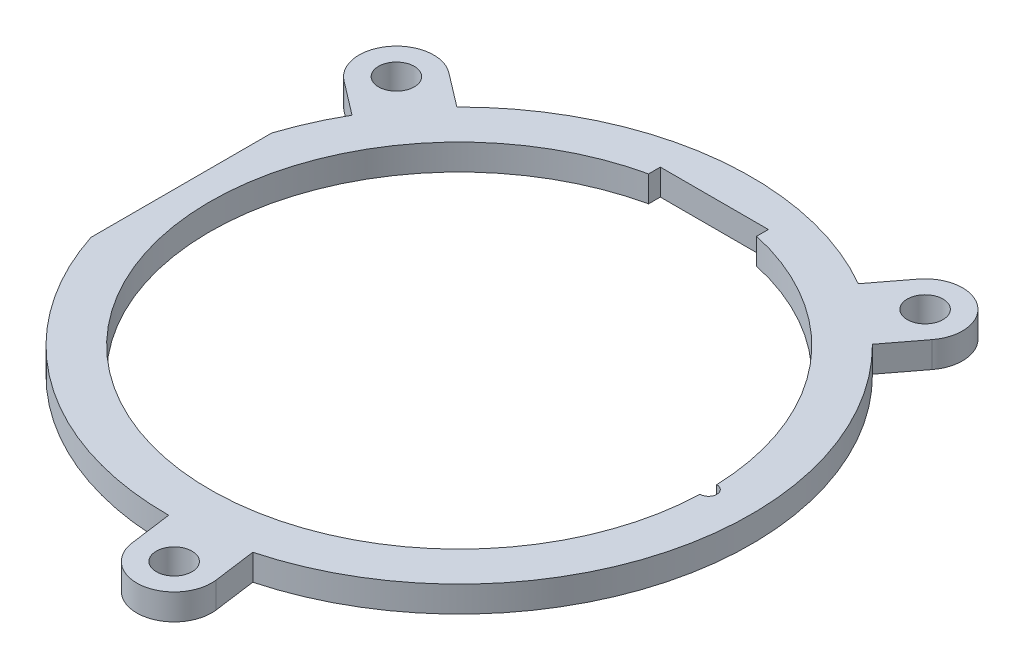
SolidWorks part; units mm, degrees
ref_plane "Front" through (0, 0, 0) normal (0, 0, 1) x (1, 0, 0)
ref_plane "Top" through (0, 0, 0) normal (0, 1, 0) x (1, 0, 0)
ref_plane "Right" through (0, 0, 0) normal (1, 0, 0) x (0, 0, -1)
sketch "Sketch1" plane through (0, 0, 0) normal (0, 1, 0) x (1, 0, 0)
  line L0 (0, -15.24) -> (0, 15.5956) construction
  line L1 (-3.302, 15.5956) -> (3.302, 15.5956)
  line L2 (-3.302, 15.5956) -> (-3.302, 14.878)
  line L3 (3.302, 15.5956) -> (3.302, 14.878)
  circle A0 centre (0, 0) radius 15.24
  circle A1 centre (0, 0) radius 21.59
  dimension "D1" = 30.48
  dimension "D3" = 30.8356
  dimension "D4" = 6.604
  dimension "D2" = 6.35
extrude "Boss-Extrude1" add sketch "Sketch1" along normal mid plane 1.5875 contours A1 A0 L2 L1 L3 region at (-20.9793, 0, 0)
sketch "Sketch2" plane through (0, 0.7937, 0) normal (0, 1, 0) x (1, 0, 0)
  line L0 (0, 18.415) -> (0, -18.415) construction
  line L1 (0, -15.24) -> (0, -21.59) construction
  circle A0 centre (0, 18.415) radius 1.4224
  circle A1 centre (0, -18.415) radius 1.4224
  arc A2 (-3.302, 14.878) -> (3.302, 14.878) centre (0, 0) ccw construction
  circle A3 centre (0, 0) radius 21.59 construction
  dimension "D1" = 2.8448
extrude "Cut-Extrude1" cut sketch "Sketch2" against normal through all
sketch "Sketch3" plane through (0, 0.7937, 0) normal (0, 1, 0) x (1, 0, 0)
  line L0 (-20.8712, 5.5245) -> (-16.9841, 5.5245)
  line L1 (-16.9841, 5.5245) -> (-16.9841, -5.5245)
  line L2 (-16.9841, -5.5245) -> (-20.8712, -5.5245)
  line L3 (-16.9841, -5.5245) -> (-20.8712, -5.5245) construction
  line L4 (-20.8712, 5.5245) -> (-16.9841, 5.5245) construction
  circle A0 centre (0, 0) radius 21.59 construction
  arc A1 (-20.8712, 5.5245) -> (-20.8712, -5.5245) centre (0, 0) ccw
extrude "Cut-Extrude2" cut sketch "Sketch3" against normal through all
sketch "Sketch4" plane through (0, 0.7937, 0) normal (0, 1, 0) x (1, 0, 0)
  line L0 (15.748, 0) -> (-15.24, 0) construction
  circle A0 centre (15.24, 0) radius 0.508
  arc A1 (-3.302, 14.878) -> (3.302, 14.878) centre (0, 0) ccw construction
  dimension "D1" = 30.988
extrude "Cut-Extrude3" cut sketch "Sketch4" against normal through all
sketch "Sketch5" plane through (0, 0.7937, 0) normal (0, 1, 0) x (1, 0, 0)
  line L0 (-12.3201, -16.1591) -> (12.3201, 16.1591) construction
  line L1 (-13.8351, -15.0041) -> (10.8052, 17.3141)
  line L2 (-10.8052, -17.3141) -> (13.8351, 15.0041)
  line L3 (16.1591, -12.3201) -> (-16.1591, 12.3201) construction
  line L4 (15.0041, -13.8351) -> (-17.3141, 10.8052)
  line L5 (17.3141, -10.8052) -> (-15.0041, 13.8351)
  line L6 (0, 0) -> (2.7145, -20.1379) construction
  line L7 (1.8879, 0.2545) -> (4.6025, -19.8834)
  line L8 (-1.8879, -0.2545) -> (0.8266, -20.3924)
  line L9 (-16.1591, 12.3201) -> (12.3201, 16.1591) construction
  circle A0 centre (0, 0) radius 17.86
  arc A1 (-13.8351, -15.0041) -> (-10.8052, -17.3141) centre (-12.3201, -16.1591) ccw
  arc A2 (13.8351, 15.0041) -> (10.8052, 17.3141) centre (12.3201, 16.1591) ccw
  circle A3 centre (12.3201, 16.1591) radius 1.0922
  circle A4 centre (-12.3201, -16.1591) radius 1.0922
  arc A5 (15.0041, -13.8351) -> (17.3141, -10.8052) centre (16.1591, -12.3201) ccw
  arc A6 (-15.0041, 13.8351) -> (-17.3141, 10.8052) centre (-16.1591, 12.3201) ccw
  circle A7 centre (-16.1591, 12.3201) radius 1.0922
  circle A8 centre (16.1591, -12.3201) radius 1.0922
  arc A9 (1.8879, 0.2545) -> (-1.8879, -0.2545) centre (0, 0) ccw
  arc A10 (0.8266, -20.3924) -> (4.6025, -19.8834) centre (2.7145, -20.1379) ccw
  circle A11 centre (2.7145, -20.1379) radius 1.0922
  arc A12 (16.1591, -12.3201) -> (2.7145, -20.1379) centre (0, 0) cw construction
  point P6 (0, 0)
  point P17 (0, 0)
  point P26 (1.3573, -10.0689)
  line M7 (-20.8712, 5.5245) -> (-16.9841, 5.5245)
  line M9 (-16.9841, -5.5245) -> (-20.8712, -5.5245)
  arc M10 (-20.8712, -5.5245) -> (-20.8712, 5.5245) centre (0, 0) ccw
  circle M11 centre (0, -18.415) radius 1.4224
  circle M12 centre (0, 18.415) radius 1.4224
  dimension "D2" = 3.81
  dimension "D1" = 3.81
extrude "Cut-Extrude4" cut sketch "Sketch5" against normal through all contours A6 L5 A0 L1 A2 M12 M10 | A6 A0 L4 M10 M7 | A1 L1 A0 M9 M10 | A5 L4 A0 L2 A1 M11 M10 | A5 A2 L2 A0 L5 M10 | A7 | A3 | A4 | A1 L2 A0 L1 A4 M10 | A11 | A5 L5 A0 L4 A8 M10 | A8 | A10 A5 L4 A0 L7 M10 region at (-16.6582, 0.7937, 10.306) region at (-13.002, 0.7937, 14.0284) region at (-5.4053, 0.7937, 18.8788) region at (-18.0946, 0.7937, -8.0783) region at (-2.5586, 0.7937, -18.0617) region at (9.8123, 0.7937, 16.8747) region at (15.6105, 0.7937, 14.0703) region at (18.0927, 0.7937, -2.4389) region at (12.3201, 0.7937, -16.1591) region at (-12.3201, 0.7937, 16.1591) region at (-16.1591, 0.7937, -12.3201) region at (16.1591, 0.7937, 12.3201) region at (2.7145, 0.7937, 20.1379)
extrude "Boss-Extrude2" add sketch "Sketch5<3>" against normal up to vertex contours A6 M10 | A2 M10 | A0 M11 | A0 M12 | A0 L8 M11 | L8 A0 M11 | A10 M10 region at (-0.2829, 0.7937, 17.4804) region at (2.9174, 0.7937, 21.6425) region at (-17.3665, 0.7937, -13.2407) region at (0, 0.7937, -17.4932) region at (0.7535, 0.7937, 17.5272) region at (0.9598, 0.7937, 18.5708) region at (13.2407, 0.7937, -17.3665) up to point (15.2315, -0.7937, 0.5079)
sketch "Sketch5<3>" plane through (0, 0.7937, 0) normal (0, 1, 0) x (1, 0, 0) same geometry as "Sketch5"
sketch "Sketch6" plane through (0, 0.7937, 0) normal (0, 1, 0) x (1, 0, 0)
  line L4 (4.9801, -19.8325) -> (4.6378, -17.2935)
  line L5 (0.1068, -17.9043) -> (0.449, -20.4433)
  line L6 (4.9801, -19.8325) -> (4.6318, -17.2489)
  line L7 (0.1008, -17.8597) -> (0.449, -20.4433)
  line L10 (-14.7731, 14.138) -> (-12.7358, 12.5847)
  line L11 (-15.5078, 8.9489) -> (-17.5451, 10.5023)
  line L12 (-14.7731, 14.138) -> (-12.7, 12.5574)
  line L13 (-15.472, 8.9216) -> (-17.5451, 10.5023)
  line L16 (14.138, 14.7731) -> (12.5847, 12.7358)
  line L17 (8.9489, 15.5078) -> (10.5023, 17.5451)
  line L18 (14.138, 14.7731) -> (12.5574, 12.7)
  line L19 (8.9216, 15.472) -> (10.5023, 17.5451)
  arc A2 (0.449, -20.4433) -> (4.9801, -19.8325) centre (2.7145, -20.1379) ccw
  arc A3 (0.449, -20.4433) -> (4.9801, -19.8325) centre (2.7145, -20.1379) ccw
  arc A5 (-14.7731, 14.138) -> (-17.5451, 10.5023) centre (-16.1591, 12.3201) ccw
  arc A6 (-14.7731, 14.138) -> (-17.5451, 10.5023) centre (-16.1591, 12.3201) ccw
  circle A7 centre (0, 0) radius 17.86
  arc A8 (14.138, 14.7731) -> (10.5023, 17.5451) centre (12.3201, 16.1591) ccw
  arc A9 (14.138, 14.7731) -> (10.5023, 17.5451) centre (12.3201, 16.1591) ccw
  line M19 (12.2818, 12.9668) -> (13.8351, 15.0041)
  arc M20 (13.8351, 15.0041) -> (10.8052, 17.3141) centre (12.3201, 16.1591) ccw
  line M21 (10.8052, 17.3141) -> (9.2519, 15.2768)
  arc M22 (9.2519, 15.2768) -> (-12.9668, 12.2818) centre (0, 0) ccw
  line M23 (-12.9668, 12.2818) -> (-15.0041, 13.8351)
  arc M24 (-15.0041, 13.8351) -> (-17.3141, 10.8052) centre (-16.1591, 12.3201) ccw
  line M25 (-17.3141, 10.8052) -> (-15.2768, 9.2519)
  arc M26 (-15.2768, 9.2519) -> (-16.9841, 5.5245) centre (0, 0) ccw
  arc M28 (-16.9841, -5.5245) -> (0.4844, -17.8534) centre (0, 0) ccw
  line M29 (0.4844, -17.8534) -> (0.8266, -20.3924)
  arc M30 (0.8266, -20.3924) -> (4.6025, -19.8834) centre (2.7145, -20.1379) ccw
  line M31 (4.6025, -19.8834) -> (4.2602, -17.3444)
  arc M32 (4.2602, -17.3444) -> (12.2818, 12.9668) centre (0, 0) ccw
  dimension "D1" = 0.381
  dimension "D2" = 0.381
  dimension "D3" = 0.381
extrude "Boss-Extrude3" add sketch "Sketch6" against normal up to vertex contours L7 A3 L6 M32 M31 M30 M29 M28 | L18 A9 L19 M22 M21 M20 M19 M32 | L12 A6 L13 M26 M25 M24 M23 M22 region at (3.0104, 0.7937, 22.3327) region at (12.4765, 0.7937, -12.8922) region at (-15.4409, 0.7937, -8.9996) up to point (-3.302, -0.7937, -14.878)
